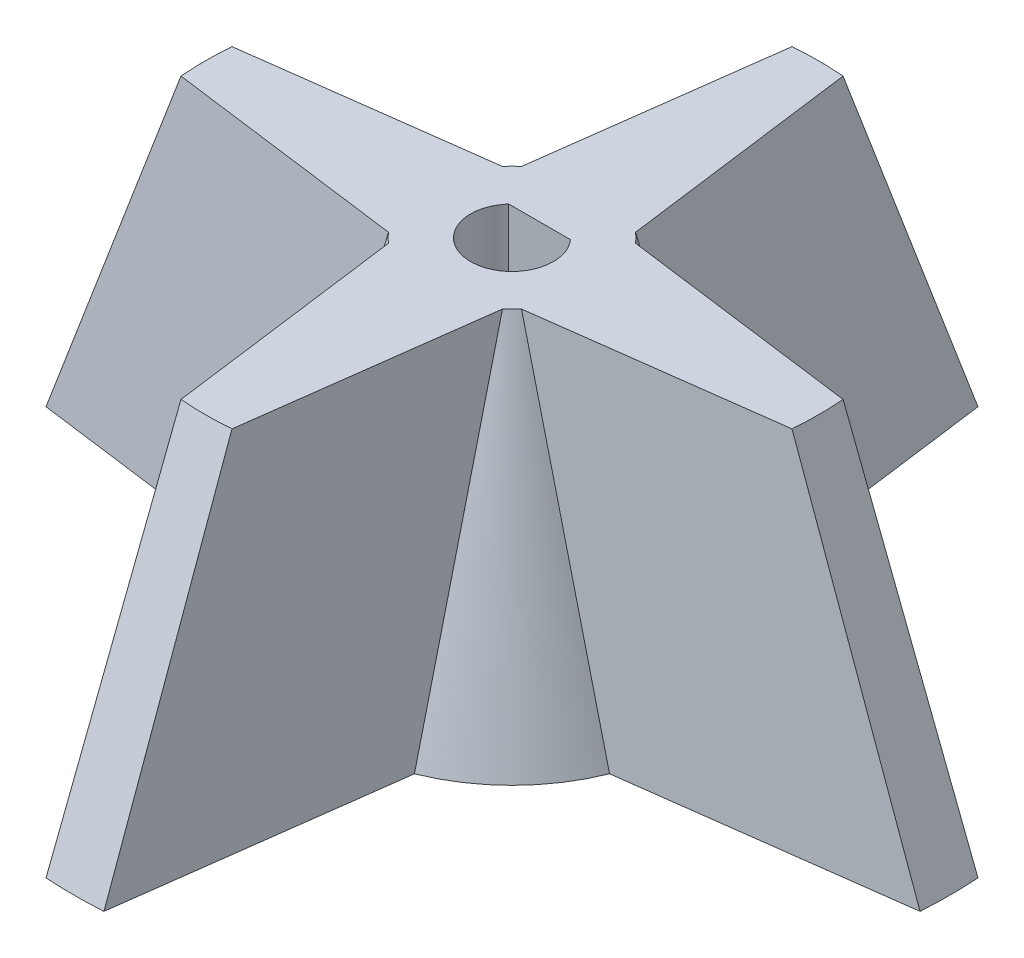
SolidWorks part; units mm, degrees
ref_plane "Front Plane" through (0, 0, 0) normal (0, 0, 1) x (1, 0, 0)
ref_plane "Top Plane" through (0, 0, 0) normal (0, 1, 0) x (1, 0, 0)
ref_plane "Right Plane" through (0, 0, 0) normal (1, 0, 0) x (0, 0, -1)
ref_plane "Plane1" through (0, 25.4, 0) normal (0, 1, 0) x (1, 0, 0)
sketch "Sketch2" plane through (0, 0, 0) normal (0, 1, 0) x (1, 0, 0)
  line L0 (-125.638, 0) -> (125.638, 0) construction
  line L1 (0, -124.5331) -> (0, 124.5331) construction
  line L2 (-4.7185, 11.7909) -> (-2.1, 31.6805)
  line L3 (2.1, 31.6805) -> (4.7185, 11.7909)
  line L4 (11.7909, 4.7185) -> (31.6805, 2.1)
  line L5 (11.7909, -4.7185) -> (31.6805, -2.1)
  line L6 (4.7185, -11.7909) -> (2.1, -31.6805)
  line L7 (-2.1, -31.6805) -> (-4.7185, -11.7909)
  line L8 (-31.6805, -2.1) -> (-11.7909, -4.7185)
  line L9 (-31.6805, 2.1) -> (-11.7909, 4.7185)
  line L10 (-12.9497, 98.3629) -> (-12.0939, 91.8622) construction
  line L12 (0, 88.5098) -> (0, -49911.4902) construction
  line L15 (-2.2361, 2) -> (2.2361, 2)
  arc A2 (4.7185, 11.7909) -> (11.7909, 4.7185) centre (0, 0) cw
  arc A3 (4.7185, -11.7909) -> (11.7909, -4.7185) centre (0, 0) ccw
  arc A4 (-11.7909, -4.7185) -> (-4.7185, -11.7909) centre (0, 0) ccw
  arc A5 (-4.7185, 11.7909) -> (-11.7909, 4.7185) centre (0, 0) ccw
  arc A6 (-2.1, 31.6805) -> (2.1, 31.6805) centre (0, 0) cw
  arc A7 (31.6805, 2.1) -> (31.6805, -2.1) centre (0, 0) cw
  arc A8 (2.1, -31.6805) -> (-2.1, -31.6805) centre (0, 0) cw
  arc A9 (-31.6805, -2.1) -> (-31.6805, 2.1) centre (0, 0) cw
  arc A10 (2.2361, 2) -> (-2.2361, 2) centre (0, 0) cw
  point P2 (0, 0)
  point P28 (-31.75, 0)
  point P29 (31.75, 0)
  point P30 (0, 31.75)
  point P31 (0, -31.75)
  dimension "D5" = 31.75
  dimension "D6" = 12.7
  dimension "D8" = 3
  dimension "D1" = 7.5
  dimension "D7" = 4.2
  dimension "D9" = 2
sketch "Sketch5" plane through (0, 25.4, 0) normal (0, 1, 0) x (1, 0, 0)
  line L0 (-4.1309, 4.8227) -> (-1.85, 22.1479)
  line L1 (1.85, 22.1479) -> (4.1309, 4.8227)
  line L2 (4.8227, 4.1309) -> (22.1479, 1.85)
  line L3 (4.8227, -4.1309) -> (22.1479, -1.85)
  line L4 (4.1309, -4.8227) -> (1.85, -22.1479)
  line L5 (-4.1309, -4.8227) -> (-1.85, -22.1479)
  line L6 (-22.1479, -1.85) -> (-4.8227, -4.1309)
  line L7 (-22.1479, 1.85) -> (-4.8227, 4.1309)
  line L8 (-4.7185, 11.7909) -> (-2.1, 31.6805) construction
  arc A0 (-1.85, 22.1479) -> (1.85, 22.1479) centre (0, 0) cw
  arc A1 (22.1479, 1.85) -> (22.1479, -1.85) centre (0, 0) cw
  arc A2 (1.85, -22.1479) -> (-1.85, -22.1479) centre (0, 0) cw
  arc A3 (-22.1479, -1.85) -> (-22.1479, 1.85) centre (0, 0) cw
  arc A4 (4.1309, 4.8227) -> (4.8227, 4.1309) centre (0, 0) cw
  arc A5 (4.8227, -4.1309) -> (4.1309, -4.8227) centre (0, 0) cw
  arc A6 (-4.1309, -4.8227) -> (-4.8227, -4.1309) centre (0, 0) cw
  arc A7 (-4.8227, 4.1309) -> (-4.1309, 4.8227) centre (0, 0) cw
  point P19 (-22.225, 0)
  point P20 (22.225, 0)
  dimension "D1" = 22.225
  dimension "D2" = 6.35
  dimension "D3" = 3.7
loft "Loft1" add section "Sketch2" section "Sketch5" connector at (31.6805, 0, 2.1) connector at (22.1479, 25.4, 1.85)
extrude "Cut-Extrude1" cut sketch "Sketch2<3>" against normal through all both and the other way through all contours A10 L15 region at (0, 0, 0.296)
sketch "Sketch2<3>" plane through (0, 0, 0) normal (0, 1, 0) x (1, 0, 0) same geometry as "Sketch2"
